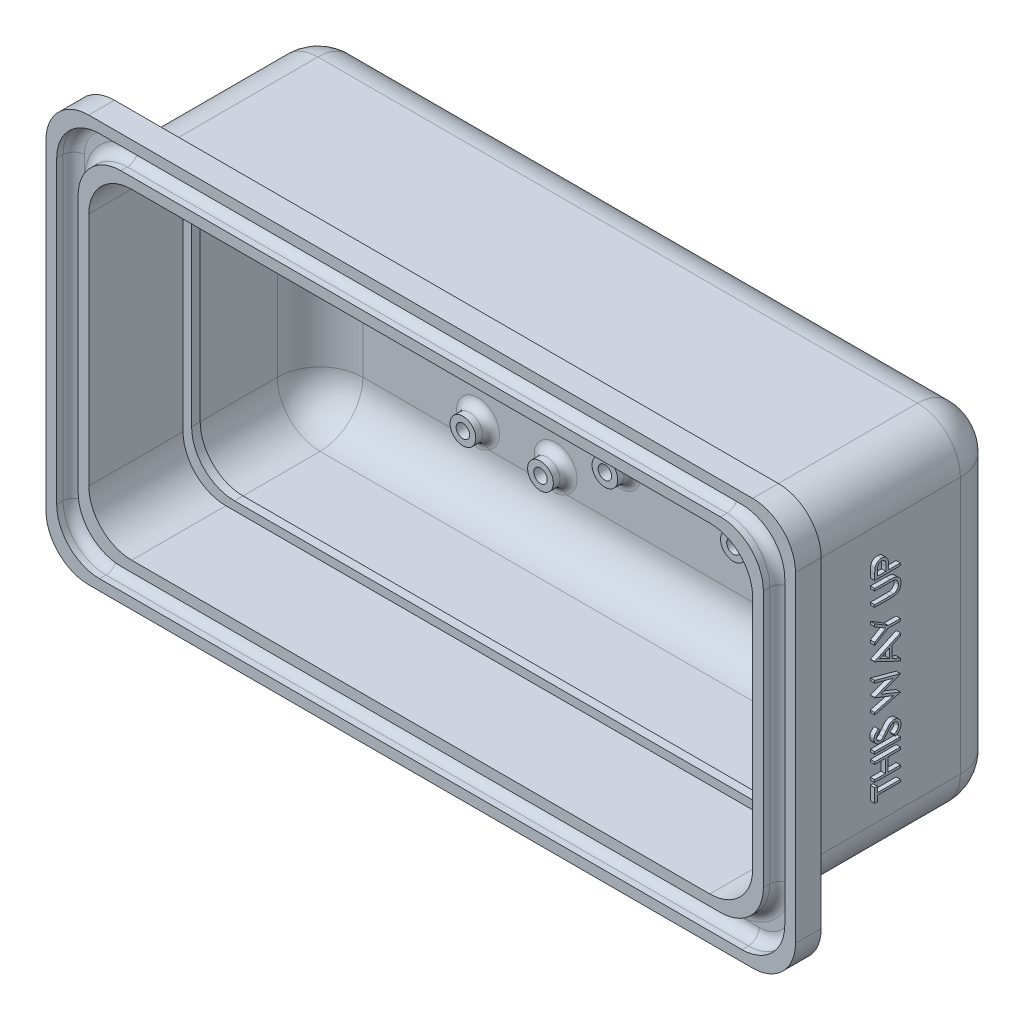
SolidWorks part; units mm, degrees
material "ABS"
ref_plane "Front Plane" through (0, 0, 0) normal (0, 0, 1) x (1, 0, 0)
ref_plane "Top Plane" through (0, 0, 0) normal (0, 1, 0) x (1, 0, 0)
ref_plane "Right Plane" through (0, 0, 0) normal (1, 0, 0) x (0, 0, -1)
sketch "Sketch1" plane through (0, 0, 0) normal (0, 0, 1) x (1, 0, 0)
  line L1 (0, 0) -> (203.2, 0)
  line L2 (0, 0) -> (0, 101.6)
  line L3 (0, 101.6) -> (203.2, 101.6)
  line L4 (203.2, 0) -> (203.2, 101.6)
  line L5 (0, 0) -> (0, 101.6)
  line L9 (203.2, 0) -> (203.2, 101.6)
  dimension "D1" = 203.2
  dimension "D2" = 101.6
extrude "Boss-Extrude1" add sketch "Sketch1" along normal blind 63.5 contours L5 L1 | L1 L3 L2 | L5 L3 | L1 L3 | L9 L3 | L1 L4 L3 | L9 L1 region at (101.6, 50.8, 0)
sketch "Sketch2" plane through (0, 0, 63.5) normal (0, 0, 1) x (1, 0, 0)
  line L0 (203.2, 0) -> (203.2, 101.6) construction
  line L1 (3.175, 3.175) -> (200.025, 3.175)
  line L2 (3.175, 3.175) -> (3.175, 98.425)
  line L3 (3.175, 98.425) -> (200.025, 98.425)
  line L4 (200.025, 3.175) -> (200.025, 98.425)
  line L6 (0, 101.6) -> (203.2, 101.6) construction
  line L7 (0, 0) -> (0, 101.6) construction
  dimension "D1" = 3.175
  dimension "D2" = 95.25
  dimension "D3" = 3.175
  dimension "D4" = 3.175
extrude "Cut-Extrude1" cut sketch "Sketch2" against normal blind 60.96
fillet "Fillet1" radius 12.7 16 edges at (203.2, 50.8, 0) (101.6, 101.6, 0) (0, 50.8, 0) (101.6, 0, 0) (101.6, 98.425, 2.54) (200.025, 50.8, 2.54) (101.6, 3.175, 2.54) (3.175, 50.8, 2.54) (200.025, 3.175, 33.02) (203.2, 0, 31.75) (200.025, 98.425, 33.02) (203.2, 101.6, 31.75) (0, 101.6, 31.75) (3.175, 98.425, 33.02) (0, 0, 31.75) (3.175, 3.175, 33.02)
sketch "Sketch3" plane through (0, 0, 63.5) normal (0, 0, 1) x (1, 0, 0)
  line L0 (3.175, 15.875) -> (3.175, 85.725) construction
  line L1 (3.175, 111.125) -> (200.025, 111.125)
  line L2 (-9.525, 98.425) -> (-9.525, 3.175)
  line L3 (3.175, -9.525) -> (200.025, -9.525)
  line L4 (212.725, 98.425) -> (212.725, 3.175)
  line L5 (15.875, 98.425) -> (187.325, 98.425)
  line L6 (3.175, 85.725) -> (3.175, 15.875)
  line L7 (15.875, 3.175) -> (187.325, 3.175)
  line L8 (200.025, 85.725) -> (200.025, 15.875)
  line L9 (187.325, 98.425) -> (15.875, 98.425) construction
  line L10 (200.025, 85.725) -> (200.025, 15.875) construction
  line L11 (187.325, 3.175) -> (15.875, 3.175) construction
  arc A0 (200.025, -9.525) -> (212.725, 3.175) centre (200.025, 3.175) ccw
  arc A1 (212.725, 98.425) -> (200.025, 111.125) centre (200.025, 98.425) ccw
  arc A2 (3.175, 111.125) -> (-9.525, 98.425) centre (3.175, 98.425) ccw
  arc A3 (3.175, -9.525) -> (-9.525, 3.175) centre (3.175, 3.175) cw
  arc A4 (3.175, 15.875) -> (15.875, 3.175) centre (15.875, 15.875) ccw
  arc A5 (187.325, 3.175) -> (200.025, 15.875) centre (187.325, 15.875) ccw
  arc A6 (200.025, 85.725) -> (187.325, 98.425) centre (187.325, 85.725) ccw
  arc A7 (15.875, 98.425) -> (3.175, 85.725) centre (15.875, 85.725) ccw
  dimension "D9" = 12.7
  dimension "D1" = 12.7
  dimension "D2" = 12.7
  dimension "D3" = 12.7
  dimension "D4" = 12.7
  dimension "D5" = 0
  dimension "D6" = 0
  dimension "D7" = 0
  dimension "D8" = 0
extrude "Boss-Extrude2" add sketch "Sketch3" along normal blind 7.62
sketch "Sketch5" plane through (0, 0, 71.12) normal (0, 0, 1) x (1, 0, 0)
  line L0 (200.025, 85.725) -> (200.025, 15.875) construction
  line L1 (12.7, 0) -> (190.5, 0)
  line L2 (0, 12.7) -> (0, 88.9)
  line L3 (12.7, 101.6) -> (190.5, 101.6)
  line L4 (203.2, 12.7) -> (203.2, 88.9)
  line L5 (6.35, -6.35) -> (196.85, -6.35)
  line L6 (-6.35, 6.35) -> (-6.35, 95.25)
  line L7 (6.35, 107.95) -> (196.85, 107.95)
  line L8 (209.55, 6.35) -> (209.55, 95.25)
  line L9 (187.325, 3.175) -> (15.875, 3.175) construction
  line L10 (187.325, 98.425) -> (15.875, 98.425) construction
  line L11 (3.175, 85.725) -> (3.175, 15.875) construction
  arc A0 (196.85, 107.95) -> (209.55, 95.25) centre (196.85, 95.25) cw
  arc A1 (190.5, 101.6) -> (203.2, 88.9) centre (190.5, 88.9) cw
  arc A2 (190.5, 0) -> (203.2, 12.7) centre (190.5, 12.7) ccw
  arc A3 (196.85, -6.35) -> (209.55, 6.35) centre (196.85, 6.35) ccw
  arc A4 (-6.35, 95.25) -> (6.35, 107.95) centre (6.35, 95.25) cw
  arc A5 (0, 88.9) -> (12.7, 101.6) centre (12.7, 88.9) cw
  arc A6 (0, 12.7) -> (12.7, 0) centre (12.7, 12.7) ccw
  arc A7 (-6.35, 6.35) -> (6.35, -6.35) centre (6.35, 6.35) ccw
  dimension "D9" = 12.7
  dimension "D1" = 6.35
  dimension "D2" = 6.35
  dimension "D3" = 6.35
  dimension "D4" = 6.35
  dimension "D5" = 3.175
  dimension "D6" = 3.175
  dimension "D7" = 3.175
  dimension "D8" = 3.175
extrude "Cut-Extrude2" cut sketch "Sketch5" against normal blind 5.08
fillet "Fillet2" radius 3.175 16 edges at (209.55, 50.8, 66.04) (205.8303, -2.6303, 66.04) (101.6, -6.35, 66.04) (-2.6303, -2.6303, 66.04) (-6.35, 50.8, 66.04) (-2.6303, 104.2303, 66.04) (101.6, 107.95, 66.04) (205.8303, 104.2303, 66.04) (101.6, 101.6, 66.04) (3.7197, 97.8803, 66.04) (0, 50.8, 66.04) (3.7197, 3.7197, 66.04) (101.6, 0, 66.04) (199.4803, 3.7197, 66.04) (203.2, 50.8, 66.04) (199.4803, 97.8803, 66.04)
sketch "Sketch6" plane through (0, 0, 0) normal (0, 0, -1) x (-1, 0, 0)
  line L1 (-212.725, 3.175) -> (-212.725, 98.425) construction
  line L2 (-3.175, -9.525) -> (-200.025, -9.525) construction
  circle A0 centre (-161.925, 50.8) radius 12.065
  dimension "D2" = 24.13
  dimension "D1" = 60.325
  dimension "D3" = 50.8
extrude "Cut-Extrude3" cut sketch "Sketch6" against normal blind 6.35
sketch "Sketch7" plane through (0, 0, 2.54) normal (0, 0, 1) x (1, 0, 0)
  circle A0 centre (161.925, 64.77) radius 0.875
  circle A1 centre (161.925, 36.83) radius 0.875
  circle A2 centre (161.925, 50.8) radius 12.065 construction
  arc A3 (163.483, 62.764) -> (160.367, 62.764) centre (161.925, 64.77) ccw
  arc A4 (160.367, 38.836) -> (163.483, 38.836) centre (161.925, 36.83) ccw
  arc A5 (160.367, 38.836) -> (163.483, 38.836) centre (161.925, 50.8) ccw
  arc A6 (163.483, 62.764) -> (160.367, 62.764) centre (161.925, 50.8) ccw
  dimension "D3" = 1.75
  dimension "D1" = 27.94
  dimension "D2" = 13.97
extrude "Boss-Extrude3" add sketch "Sketch7" along normal blind 2.54
extrude "Cut-Extrude4" cut sketch "Sketch7<2>" against normal blind 1.27 contours A0 region at (161.925, 64.77, 2.54)
sketch "Sketch7<2>" plane through (0, 0, 2.54) normal (0, 0, 1) x (1, 0, 0) same geometry as "Sketch7"
sketch "Sketch8" plane through (0, 0, 2.54) normal (0, 0, 1) x (1, 0, 0)
  line L8 (200.025, 111.125) -> (3.175, 111.125) construction
  circle A1 centre (111.125, 50.8) radius 12.065
  circle A2 centre (161.925, 50.8) radius 12.065 construction
  dimension "D1" = 60.325
  dimension "D2" = 50.8
extrude "Cut-Extrude5" cut sketch "Sketch8" against normal through all contours A1
sketch "Sketch10" plane through (0, 0, 2.54) normal (0, 0, 1) x (1, 0, 0)
  line L1 (130.175, 69.85) -> (92.075, 69.85) construction
  line L2 (130.175, 69.85) -> (130.175, 31.75) construction
  line L3 (130.175, 31.75) -> (92.075, 31.75) construction
  line L4 (92.075, 69.85) -> (92.075, 31.75) construction
  circle A0 centre (111.125, 50.8) radius 12.065 construction
  circle A1 centre (130.175, 69.85) radius 3.81
  circle A2 centre (130.175, 31.75) radius 3.81
  circle A3 centre (92.075, 31.75) radius 3.81
  circle A4 centre (92.075, 69.85) radius 3.81
  circle A5 centre (130.175, 69.85) radius 2
  circle A6 centre (130.175, 31.75) radius 2
  circle A7 centre (92.075, 31.75) radius 2
  circle A8 centre (92.075, 69.85) radius 2
  dimension "D4" = 7.62
  dimension "D5" = 4
  dimension "D1" = 19.05
  dimension "D2" = 19.05
  dimension "D3" = 38.1
extrude "Boss-Extrude5" add sketch "Sketch10" along normal blind 4.445
extrude "Cut-Extrude6" cut sketch "Sketch10<2>" against normal blind 1.27 contours A5 | A6 | A8 | A7 region at (130.175, 69.85, 2.54) region at (130.175, 31.75, 2.54) region at (92.075, 31.75, 2.54) region at (92.075, 69.85, 2.54)
sketch "Sketch10<2>" plane through (0, 0, 2.54) normal (0, 0, 1) x (1, 0, 0) same geometry as "Sketch10"
ref_plane "Plane1" through (0, 0, 40.64) normal (0, 0, 1) x (1, 0, 0)
sketch "Sketch11" plane through (0, 0, 40.64) normal (0, 0, 1) x (1, 0, 0)
  line L0 (3.175, 15.875) -> (3.175, 85.725) construction
  line L1 (187.325, 98.425) -> (15.875, 98.425) construction
  line L2 (15.875, 3.175) -> (187.325, 3.175) construction
  line L3 (200.025, 85.725) -> (200.025, 15.875) construction
  line L4 (3.175, 15.875) -> (3.175, 85.725)
  line L5 (187.325, 98.425) -> (15.875, 98.425)
  line L6 (15.875, 3.175) -> (187.325, 3.175)
  line L7 (200.025, 85.725) -> (200.025, 15.875)
  line L9 (184.785, 95.885) -> (18.415, 95.885)
  line L10 (197.485, 83.185) -> (197.485, 18.415)
  line L11 (184.785, 5.715) -> (18.415, 5.715)
  line L12 (5.715, 83.185) -> (5.715, 18.415)
  arc A0 (3.175, 15.875) -> (15.875, 3.175) centre (15.875, 15.875) ccw construction
  arc A1 (15.875, 98.425) -> (3.175, 85.725) centre (15.875, 85.725) ccw construction
  arc A2 (187.325, 3.175) -> (200.025, 15.875) centre (187.325, 15.875) ccw construction
  arc A3 (200.025, 85.725) -> (187.325, 98.425) centre (187.325, 85.725) ccw construction
  arc A4 (3.175, 15.875) -> (15.875, 3.175) centre (15.875, 15.875) ccw
  arc A5 (15.875, 98.425) -> (3.175, 85.725) centre (15.875, 85.725) ccw
  arc A6 (187.325, 3.175) -> (200.025, 15.875) centre (187.325, 15.875) ccw
  arc A7 (200.025, 85.725) -> (187.325, 98.425) centre (187.325, 85.725) ccw
  arc A8 (184.785, 95.885) -> (197.485, 83.185) centre (184.785, 83.185) cw
  arc A9 (197.485, 18.415) -> (184.785, 5.715) centre (184.785, 18.415) cw
  arc A10 (18.415, 5.715) -> (5.715, 18.415) centre (18.415, 18.415) cw
  arc A11 (18.415, 95.885) -> (5.715, 83.185) centre (18.415, 83.185) ccw
  dimension "D5" = 12.7
  dimension "D1" = 2.54
  dimension "D2" = 2.54
  dimension "D3" = 2.54
  dimension "D4" = 2.54
extrude "Boss-Extrude6" add sketch "Sketch11" along normal blind 2.54
sketch "Sketch14" plane through (0, 0, 0) normal (0, -1, 0) x (1, 0, 0)
  line L0 (12.7, 63.5) -> (190.5, 63.5) construction
  line L1 (38.1, 63.5) -> (63.5, 63.5)
  line L2 (38.1, 63.5) -> (38.1, 50.8)
  line L3 (38.1, 50.8) -> (63.5, 50.8)
  line L4 (63.5, 63.5) -> (63.5, 50.8)
  line L5 (190.5, 12.7) -> (190.5, 63.5) construction
  line L6 (139.7, 63.5) -> (165.1, 63.5)
  line L7 (139.7, 63.5) -> (139.7, 50.8)
  line L8 (139.7, 50.8) -> (165.1, 50.8)
  line L9 (165.1, 63.5) -> (165.1, 50.8)
  point P10 (50.8, 63.5)
  point P11 (152.4, 63.5)
  dimension "D1" = 25.4
  dimension "D2" = 25.4
  dimension "D3" = 101.6
  dimension "D4" = 38.1
  dimension "D5" = 12.7
  dimension "D6" = 12.7
extrude "Boss-Extrude8" add sketch "Sketch14" along normal blind 17.78
fillet "Fillet5" radius 6.35 4 edges at (152.4, -17.78, 50.8) (152.4, -17.78, 63.5) (50.8, -17.78, 50.8) (50.8, -17.78, 63.5)
sketch "Sketch15" plane through (38.1, 0, 0) normal (-1, 0, 0) x (0, 0, 1)
  circle A0 centre (57.15, -11.43) radius 1.5
  dimension "D1" = 3
extrude "Cut-Extrude8" cut sketch "Sketch15" against normal through all
fillet "Fillet3" radius 2.54 6 edges at (88.265, 31.75, 2.54) (88.265, 69.85, 2.54) (126.365, 31.75, 2.54) (126.365, 69.85, 2.54) (161.925, 34.29, 2.54) (161.925, 67.31, 2.54)
sketch "Sketch16" plane through (0, 0, 2.54) normal (0, 0, 1) x (1, 0, 0)
  line L0 (187.325, 85.725) -> (15.875, 85.725) construction
  line L1 (73.025, 79.375) -> (50.025, 79.375) construction
  line L2 (73.025, 79.375) -> (73.025, 21.375) construction
  line L3 (73.025, 21.375) -> (50.025, 21.375) construction
  line L4 (50.025, 79.375) -> (50.025, 21.375) construction
  circle A0 centre (92.075, 69.85) radius 6.35 construction
  circle A1 centre (50.025, 79.375) radius 2
  circle A2 centre (73.025, 79.375) radius 2
  circle A3 centre (73.025, 21.375) radius 2
  circle A4 centre (50.025, 21.375) radius 2
  circle A5 centre (73.025, 79.375) radius 3.81
  circle A6 centre (73.025, 21.375) radius 3.81
  circle A7 centre (50.025, 21.375) radius 3.81
  circle A8 centre (50.025, 79.375) radius 3.81
  dimension "D5" = 4
  dimension "D6" = 7.62
  dimension "D1" = 58
  dimension "D2" = 23
  dimension "D3" = 19.05
  dimension "D4" = 6.35
extrude "Boss-Extrude9" add sketch "Sketch16" along normal blind 4.5 contours A5 A2 | A8 A1 | A7 A4 | A6 A3 region at (69.3228, 79.375, 2.54) region at (69.3228, 21.375, 2.54) region at (46.3228, 21.375, 2.54) region at (46.3228, 79.375, 2.54)
extrude "Cut-Extrude9" cut sketch "Sketch16<3>" against normal blind 1.5 contours A1 | A2 | A3 | A4 region at (50.025, 79.375, 2.54) region at (73.025, 79.375, 2.54) region at (73.025, 21.375, 2.54) region at (50.025, 21.375, 2.54)
sketch "Sketch16<3>" plane through (0, 0, 2.54) normal (0, 0, 1) x (1, 0, 0) same geometry as "Sketch16"
sketch "Sketch17" plane through (203.2, 0, 0) normal (1, 0, 0) x (0, 0, -1)
  line L0 (-31.75, 19.05) -> (-31.75, 82.55) construction
  line L2 (-63.5, 12.7) -> (-12.7, 12.7) construction
  line L3 (-12.7, 12.7) -> (-12.7, 88.9) construction
  text T0 "THIS WAY UP" font "Century Gothic" height 7.62
  dimension "D1" = 63.5
  dimension "D2" = 6.35
  dimension "D3" = 19.05
extrude "Boss-Extrude10" add sketch "Sketch17" along normal blind 1.27
fillet "Fillet6" radius 2.54 4 edges at (46.215, 21.375, 2.54) (69.215, 21.375, 2.54) (46.215, 79.375, 2.54) (69.215, 79.375, 2.54)
